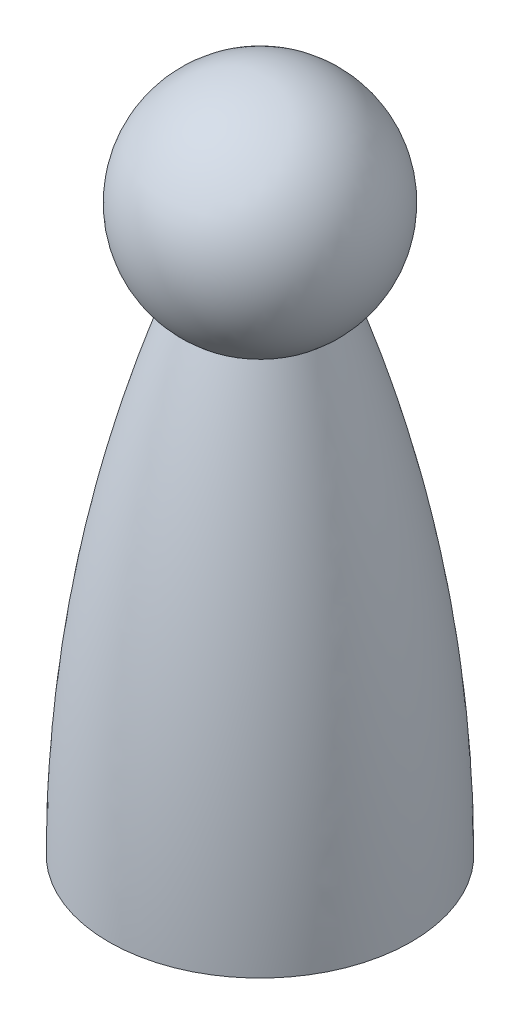
SolidWorks part; units mm, degrees
ref_plane "Front Plane" through (0, 0, 0) normal (0, 0, 1) x (1, 0, 0)
ref_plane "Top Plane" through (0, 0, 0) normal (0, 1, 0) x (1, 0, 0)
ref_plane "Right Plane" through (0, 0, 0) normal (1, 0, 0) x (0, 0, -1)
sketch "Sketch1" plane through (0, 0, 0) normal (1, 0, 0) x (0, 0, -1)
  line L0 (0, 0) -> (0, 88.9)
  line L1 (0, 0) -> (12.7, 0)
  line L2 (12.7, 0) -> (12.7, 3.81)
  line L3 (12.7, 3.81) -> (19.05, 3.81)
  arc A0 (0, 60.96) -> (0, 88.9) centre (0, 74.93) ccw
  spline S0 degree 2 poles (19.05, 3.81) (18.9607, 34.8743) (8.6595, 63.9676) knots 0 0 0 1 1 1
  point P8 (0, 0)
  point P12 (8.6595, 63.9676)
  dimension "D2" = 27.94
  dimension "D1" = 88.9
  dimension "D3" = 12.7
  dimension "D4" = 3.81
  dimension "D5" = 8.6595
  dimension "D6" = 19.6712
  dimension "D7" = 15.0745
  dimension "D8" = 6.35
revolve "Revolve1" add sketch "Sketch1" angle 360 about L0 region at (0, 28.5548, -8.1112) region at (0, 74.93, -5.9291)
